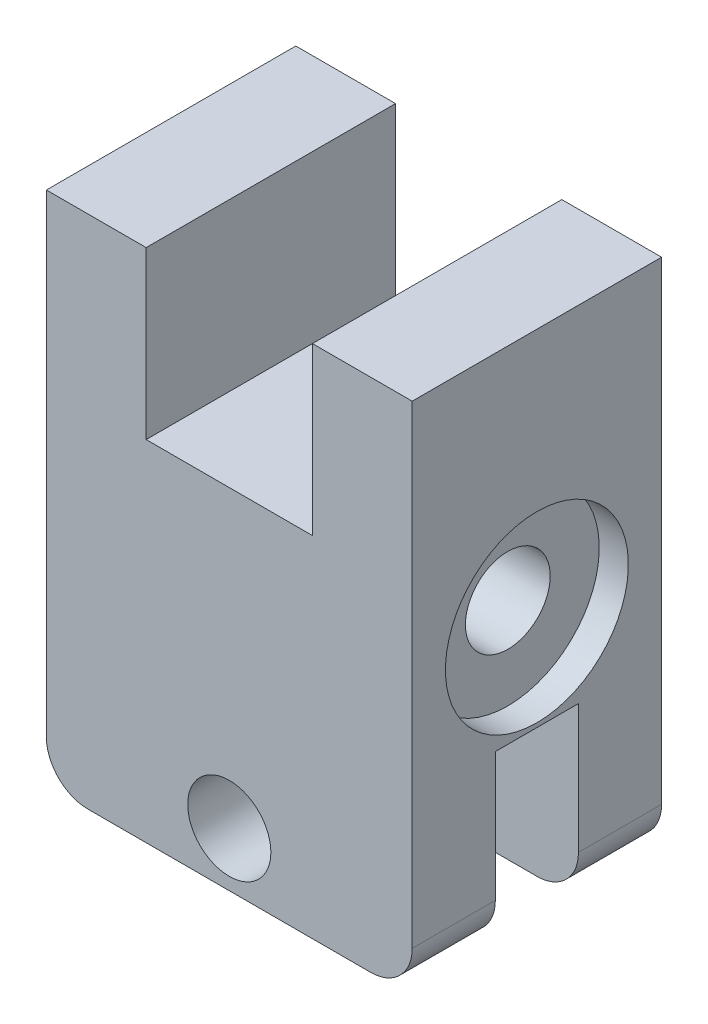
SolidWorks part; units mm, degrees
ref_plane "Alzado" through (0, 0, 0) normal (0, 0, 1) x (1, 0, 0)
ref_plane "Planta" through (0, 0, 0) normal (0, 1, 0) x (1, 0, 0)
ref_plane "Vista lateral" through (0, 0, 0) normal (1, 0, 0) x (0, 0, -1)
sketch "Croquis1" plane through (0, 0, 0) normal (0, 0, 1) x (1, 0, 0)
  line L0 (0, 25) -> (0, 0) construction
  line L1 (-22, 35) -> (22, 35)
  line L2 (-22, 35) -> (-22, -35)
  line L3 (-22, -35) -> (22, -35)
  line L4 (22, 35) -> (22, -35)
  line L5 (-22, 35) -> (22, -35) construction
  line L6 (-22, -35) -> (22, 35) construction
  line L7 (0, 0) -> (0, -20.5) construction
  line L8 (-10, 15) -> (10, 15)
  line L9 (-10, 15) -> (-10, 35)
  line L10 (-10, 35) -> (10, 35)
  line L11 (10, 15) -> (10, 35)
  line L12 (-10, 15) -> (10, 35) construction
  line L13 (-10, 35) -> (10, 15) construction
  circle A0 centre (0, -20.5) radius 5
  point P0 (0, 0)
  point P8 (0, 25)
  dimension "D4" = 10
  dimension "D1" = 20
  dimension "D2" = 20
  dimension "D3" = 50
  dimension "D5" = 20.5
  dimension "D6" = 44
extrude "Base" add sketch "Croquis1" along normal blind 30 contours L11 L8 L9 L1 L2 L3 L4 A0 region at (0, -3.2251, 0)
sketch "Croquis4" plane through (22, 0, 0) normal (1, 0, 0) x (0, 0, -1)
  line L0 (-15, 35) -> (-15, 15) construction
  line L1 (-30, 35) -> (0, 35) construction
  line L2 (-15, 15) -> (-15, 5) construction
  circle A0 centre (-15, 5) radius 5.1
  dimension "D2" = 10.2
  dimension "D1" = 20
  dimension "D3" = 10
extrude "Cortar-Extruir3" cut sketch "Croquis4" against normal through all
sketch "Croquis5" plane through (22, 0, 0) normal (1, 0, 0) x (0, 0, -1)
  circle A0 centre (-15, 5) radius 11
  dimension "D1" = 22
extrude "Cortar-Extruir4" cut sketch "Croquis5" against normal blind 3.5 contours A0
sketch "Croquis7" plane through (22, 0, 0) normal (1, 0, 0) x (0, 0, -1)
  line L0 (-15, -35) -> (-15, -6.5) construction
  line L1 (-30, -35) -> (0, -35) construction
  line L2 (-10, -35) -> (-10, -6.5)
  line L3 (-20, -35) -> (-20, -6.5)
  line L4 (-10, -6.5) -> (-20, -6.5)
  line L5 (-10, -35) -> (-20, -35)
  dimension "D1" = 5
  dimension "D3" = 28.5
  dimension "D2" = 5
extrude "Cortar-Extruir6" cut sketch "Croquis7" against normal through all
sketch "Croquis8" plane through (0, 0, 30) normal (0, 0, 1) x (1, 0, 0)
  line L0 (22, 35) -> (22, -35) construction
  line L1 (-22, -35) -> (22, -35)
  line L2 (-22, -35) -> (-22, -27)
  line L3 (-22, -27) -> (22, -27)
  line L4 (22, -35) -> (22, -27)
  dimension "D1" = 8
extrude "Cortar-Extruir7" cut sketch "Croquis8" against normal through all
fillet "Redondeo3" radius 5 4 edges at (-22, -27, 5) (-22, -27, 25) (22, -27, 5) (22, -27, 25)
